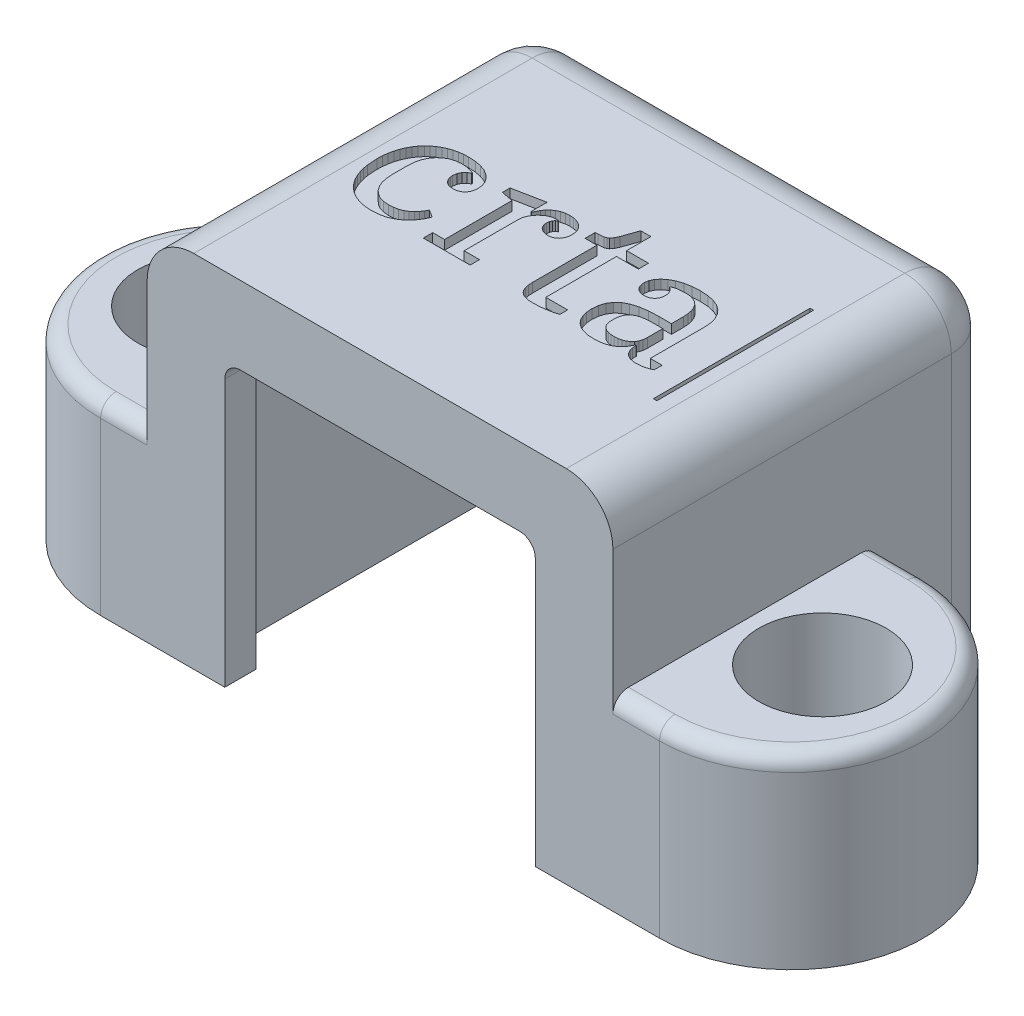
SolidWorks part; units mm, degrees
material "Custom Plastic"
ref_plane "Front Plane" through (0, 0, 0) normal (0, 0, 1) x (1, 0, 0)
ref_plane "Top Plane" through (0, 0, 0) normal (0, 1, 0) x (1, 0, 0)
ref_plane "Right Plane" through (0, 0, 0) normal (1, 0, 0) x (0, 0, -1)
sketch "Sketch1" plane through (0, 0, 0) normal (0, 0, 1) x (1, 0, 0)
  line L0 (0, -210.3757) -> (0, 10308.4069) construction
  line L1 (0, 0) -> (6, 0)
  line L2 (6, 0) -> (6, -10.1)
  line L3 (0, 1.5) -> (7.5, 1.5)
  line L4 (7.5, 1.5) -> (7.5, -10.1)
  line L5 (7.5, -10.1) -> (6, -10.1)
  line L6 (-7.5, -10.1) -> (-6, -10.1)
  line L7 (-7.5, 1.5) -> (-7.5, -10.1)
  line L8 (0, 1.5) -> (-7.5, 1.5)
  line L9 (-6, 0) -> (-6, -10.1)
  line L10 (0, 0) -> (-6, 0)
  dimension "D1" = 12
  dimension "D2" = 10.1
  dimension "D3" = 1.5
extrude "Boss-Extrude1" add sketch "Sketch1" along normal blind 12.4
sketch "Sketch3" plane through (0, -10.1, 0) normal (0, -1, 0) x (1, 0, 0)
  line L0 (0, -1000) -> (0, 49000) construction
  line L1 (7.5, 0) -> (-7.5, 0) construction
  line L2 (7.5, 3.9) -> (7.5, 12.4)
  line L3 (7.5, 12.4) -> (7.5, 0) construction
  line L4 (7.5, 3.9) -> (9, 3.9)
  line L5 (7.5, 12.4) -> (9, 12.4)
  line L6 (-7.5, 12.4) -> (-9, 12.4)
  line L7 (-7.5, 3.9) -> (-9, 3.9)
  line L8 (-7.5, 3.9) -> (-7.5, 12.4)
  arc A0 (9, 3.9) -> (9, 12.4) centre (9, 8.15) ccw
  arc A1 (-9, 3.9) -> (-9, 12.4) centre (-9, 8.15) cw
  point P5 (0, 0)
  point P10 (7.5, 8.15)
  point P22 (-7.5, 8.15)
  dimension "D1" = 8.5
  dimension "D2" = 1.5
extrude "Boss-Extrude2" add sketch "Sketch3" against normal blind 6
sketch "Sketch4" plane through (0, -10.1, 0) normal (0, -1, 0) x (1, 0, 0)
  line L1 (0, -1000) -> (0, 49000) construction
  circle A0 centre (-10, 8.15) radius 2.05
  circle A2 centre (10, 8.15) radius 2.05
  arc A3 (-9, 12.4) -> (-9, 3.9) centre (-9, 8.15) ccw construction
  point P3 (-9, 8.15)
  dimension "D1" = 4.1
  dimension "D2" = 1
extrude "Cut-Extrude1" cut sketch "Sketch4" against normal up to surface (6 mm away) up to face at (9.3125, -4.1, 8.15)
fillet "Fillet1" radius 1.5 2 edges at (-7.5, 1.5, 6.2) (7.5, 1.5, 6.2)
fillet "Fillet2" radius 0.5 6 edges at (8.25, -4.1, 3.9) (8.25, -4.1, 12.4) (13.25, -4.1, 8.15) (-8.25, -4.1, 12.4) (-13.25, -4.1, 8.15) (-8.25, -4.1, 3.9)
fillet "Fillet3" radius 1 2 edges at (-6, 0, 6.2) (6, 0, 6.2)
sketch "Sketch6" plane through (0, 0, 12.4) normal (0, 0, -1) x (-1, 0, 0)
  line L0 (6, -10.1) -> (6, -1) construction
  line L1 (5, 0) -> (-5, 0) construction
  line L2 (-6, -1) -> (-6, -10.1) construction
  line L3 (6, -10.1) -> (6, -1)
  line L4 (5, 0) -> (-5, 0)
  line L5 (-6, -1) -> (-6, -10.1)
  line L6 (5, -10.1) -> (5, -1)
  line L7 (5, -1) -> (-5, -1)
  line L8 (-5, -1) -> (-5, -10.1)
  line L9 (-5, -10.1) -> (-6, -10.1)
  line L10 (5, -10.1) -> (6, -10.1)
  arc A0 (6, -1) -> (5, 0) centre (5, -1) ccw construction
  arc A1 (-5, 0) -> (-6, -1) centre (-5, -1) ccw construction
  arc A2 (6, -1) -> (5, 0) centre (5, -1) ccw
  arc A3 (-5, 0) -> (-6, -1) centre (-5, -1) ccw
  arc A4 (5, -1) -> (5, -1) centre (5, -1) ccw
  arc A5 (-5, -1) -> (-5, -1) centre (-5, -1) ccw
  dimension "D1" = 1
extrude "Boss-Extrude3" add sketch "Sketch6" along normal blind 1
fillet "Fillet4" radius 0.5 2 edges at (-5, -1, 11.9) (5, -1, 11.9)
ref_plane "Plane1" through (0, 0, 5.55) normal (0, 0, -1) x (-1, 0, 0)
sketch "Sketch7" plane through (0, 0, 5.55) normal (0, 0, -1) x (-1, 0, 0)
  line L0 (-6, -2) -> (-4, 0)
  line L1 (-6, -1) -> (-6, -10.1) construction
  line L2 (5, 0) -> (-5, 0) construction
  line L3 (5, 0) -> (-5, 0) construction
  line L4 (-6, -1) -> (-6, -10.1) construction
  line L5 (-4, 0) -> (-5, 0)
  line L6 (-6, -1) -> (-6, -2)
  line L7 (0, -1000) -> (0, 49000) construction
  line L8 (6, -1) -> (6, -2)
  line L9 (4, 0) -> (5, 0)
  line L10 (6, -2) -> (4, 0)
  arc A0 (-5, 0) -> (-6, -1) centre (-5, -1) ccw construction
  arc A1 (-5, 0) -> (-6, -1) centre (-5, -1) ccw
  arc A2 (5, 0) -> (6, -1) centre (5, -1) cw
  dimension "D1" = 45
  dimension "D2" = 2
extrude "Boss-Extrude4" add sketch "Sketch7" along normal blind 1 contours L5 A1 L6 L0 | A2 L9 L10 L8 region at (5.28, -0.72, 5.55) region at (-5.28, -0.72, 5.55)
fillet "Fillet5" radius 1.5 5 edges at (-7.5, -5.05, 0) (-7.0607, 1.0607, 0) (0, 1.5, 0) (7.0607, 1.0607, 0) (7.5, -5.05, 0)
sketch "Sketch8" plane through (0, 1.5, 0) normal (0, 1, 0) x (1, 0, 0)
  point P306 (0, 0)
  line B0 (-4.3206, -8.3419) -> (-4.4819, -8.3349)
  line B1 (-4.4819, -8.3349) -> (-4.6341, -8.3138)
  line B2 (-4.6341, -8.3138) -> (-4.7771, -8.2786)
  line B3 (-4.7771, -8.2786) -> (-4.911, -8.2294)
  line B4 (-4.911, -8.2294) -> (-5.0326, -8.1676)
  line B5 (-5.0326, -8.1676) -> (-5.1444, -8.0945)
  line B6 (-5.1444, -8.0945) -> (-5.2463, -8.0101)
  line B7 (-5.2463, -8.0101) -> (-5.3384, -7.9146)
  line B8 (-5.3384, -7.9146) -> (-5.4203, -7.8084)
  line B9 (-5.4203, -7.8084) -> (-5.4916, -7.6924)
  line B10 (-5.4916, -7.6924) -> (-5.5524, -7.5666)
  line B11 (-5.5524, -7.5666) -> (-5.6027, -7.431)
  line B12 (-5.6027, -7.431) -> (-5.6421, -7.2869)
  line B13 (-5.6421, -7.2869) -> (-5.6702, -7.1357)
  line B14 (-5.6702, -7.1357) -> (-5.6927, -6.8124)
  line B15 (-5.6927, -6.8124) -> (-5.686, -6.6374)
  line B16 (-5.686, -6.6374) -> (-5.666, -6.4722)
  line B17 (-5.666, -6.4722) -> (-5.6326, -6.3169)
  line B18 (-5.6326, -6.3169) -> (-5.5858, -6.1714)
  line B19 (-5.5858, -6.1714) -> (-5.5271, -6.0336)
  line B20 (-5.5271, -6.0336) -> (-5.4579, -5.9071)
  line B21 (-5.4579, -5.9071) -> (-5.3781, -5.7918)
  line B22 (-5.3781, -5.7918) -> (-5.2878, -5.6878)
  line B23 (-5.2878, -5.6878) -> (-5.188, -5.5954)
  line B24 (-5.188, -5.5954) -> (-5.0797, -5.5149)
  line B25 (-5.0797, -5.5149) -> (-4.9631, -5.4463)
  line B26 (-4.9631, -5.4463) -> (-4.8379, -5.3898)
  line B27 (-4.8379, -5.3898) -> (-4.703, -5.343)
  line B28 (-4.703, -5.343) -> (-4.5624, -5.3096)
  line B29 (-4.5624, -5.3096) -> (-4.4162, -5.2896)
  line B30 (-4.4162, -5.2896) -> (-4.2644, -5.2829)
  line B31 (-4.2644, -5.2829) -> (-4.0359, -5.2956)
  line B32 (-4.0359, -5.2956) -> (-3.8342, -5.3335)
  line B33 (-3.8342, -5.3335) -> (-3.6592, -5.3968)
  line B34 (-3.6592, -5.3968) -> (-3.5109, -5.4853)
  line B35 (-3.5109, -5.4853) -> (-3.3903, -5.5936)
  line B36 (-3.3903, -5.5936) -> (-3.3042, -5.7159)
  line B37 (-3.3042, -5.7159) -> (-3.2526, -5.8523)
  line B38 (-3.2526, -5.8523) -> (-3.2353, -6.0027)
  line B39 (-3.2353, -6.0027) -> (-3.242, -6.0958)
  line B40 (-3.242, -6.0958) -> (-3.2621, -6.1784)
  line B41 (-3.2621, -6.1784) -> (-3.2954, -6.2505)
  line B42 (-3.2954, -6.2505) -> (-3.3422, -6.312)
  line B43 (-3.3422, -6.312) -> (-3.4002, -6.3587)
  line B44 (-3.4002, -6.3587) -> (-3.4673, -6.3921)
  line B45 (-3.4673, -6.3921) -> (-3.5436, -6.4121)
  line B46 (-3.5436, -6.4121) -> (-3.629, -6.4188)
  line B47 (-3.629, -6.4188) -> (-3.7161, -6.4125)
  line B48 (-3.7161, -6.4125) -> (-3.792, -6.3935)
  line B49 (-3.792, -6.3935) -> (-3.8567, -6.3619)
  line B50 (-3.8567, -6.3619) -> (-3.9101, -6.3176)
  line B51 (-3.9101, -6.3176) -> (-3.9519, -6.261)
  line B52 (-3.9519, -6.261) -> (-3.9818, -6.1981)
  line B53 (-3.9818, -6.1981) -> (-3.9997, -6.1289)
  line B54 (-3.9997, -6.1289) -> (-4.0057, -6.0533)
  line B55 (-4.0057, -6.0533) -> (-3.9889, -5.9324)
  line B56 (-3.9889, -5.9324) -> (-3.9382, -5.8284)
  line B57 (-3.9382, -5.8284) -> (-3.8609, -5.7454)
  line B58 (-3.8609, -5.7454) -> (-3.7639, -5.6878)
  line B59 (-3.7639, -5.6878) -> (-3.7639, -5.6597)
  line B60 (-3.7639, -5.6597) -> (-3.9326, -5.6091)
  line B61 (-3.9326, -5.6091) -> (-4.0465, -5.588)
  line B62 (-4.0465, -5.588) -> (-4.1857, -5.5809)
  line B63 (-4.1857, -5.5809) -> (-4.3628, -5.5978)
  line B64 (-4.3628, -5.5978) -> (-4.5231, -5.6484)
  line B65 (-4.5231, -5.6484) -> (-4.6636, -5.73)
  line B66 (-4.6636, -5.73) -> (-4.7817, -5.8396)
  line B67 (-4.7817, -5.8396) -> (-4.8773, -5.9703)
  line B68 (-4.8773, -5.9703) -> (-4.9504, -6.1264)
  line B69 (-4.9504, -6.1264) -> (-4.9926, -6.3049)
  line B70 (-4.9926, -6.3049) -> (-5.0066, -6.5031)
  line B71 (-5.0066, -6.5031) -> (-5.0066, -6.9924)
  line B72 (-5.0066, -6.9924) -> (-4.9936, -7.1923)
  line B73 (-4.9936, -7.1923) -> (-4.9546, -7.3705)
  line B74 (-4.9546, -7.3705) -> (-4.8896, -7.5269)
  line B75 (-4.8896, -7.5269) -> (-4.7986, -7.6615)
  line B76 (-4.7986, -7.6615) -> (-4.6851, -7.7673)
  line B77 (-4.6851, -7.7673) -> (-4.5526, -7.8429)
  line B78 (-4.5526, -7.8429) -> (-4.4011, -7.8882)
  line B79 (-4.4011, -7.8882) -> (-4.2306, -7.9033)
  line B80 (-4.2306, -7.9033) -> (-4.0714, -7.8942)
  line B81 (-4.0714, -7.8942) -> (-3.9312, -7.8668)
  line B82 (-3.9312, -7.8668) -> (-3.81, -7.8211)
  line B83 (-3.81, -7.8211) -> (-3.7077, -7.7571)
  line B84 (-3.7077, -7.7571) -> (-3.6177, -7.6798)
  line B85 (-3.6177, -7.6798) -> (-3.539, -7.594)
  line B86 (-3.539, -7.594) -> (-3.4715, -7.4998)
  line B87 (-3.4715, -7.4998) -> (-3.4153, -7.3972)
  line B88 (-3.4153, -7.3972) -> (-3.1735, -7.5434)
  line B89 (-3.1735, -7.5434) -> (-3.2354, -7.6882)
  line B90 (-3.2354, -7.6882) -> (-3.3197, -7.8302)
  line B91 (-3.3197, -7.8302) -> (-3.4265, -7.9652)
  line B92 (-3.4265, -7.9652) -> (-3.5559, -8.0889)
  line B93 (-3.5559, -8.0889) -> (-3.7091, -8.1915)
  line B94 (-3.7091, -8.1915) -> (-3.8876, -8.2744)
  line B95 (-3.8876, -8.2744) -> (-4.0915, -8.325)
  line B96 (-4.0915, -8.325) -> (-4.3206, -8.3419)
  line B97 (-2.7326, -7.9708) -> (-2.3502, -7.9708)
  line B98 (-2.3502, -7.9708) -> (-2.3502, -5.8002)
  line B99 (-2.3502, -5.8002) -> (-2.7326, -5.7271)
  line B100 (-2.7326, -5.7271) -> (-2.7326, -5.4797)
  line B101 (-2.7326, -5.4797) -> (-1.7373, -5.2829)
  line B102 (-1.7373, -5.2829) -> (-1.7373, -5.8059)
  line B103 (-1.7373, -5.8059) -> (-1.7091, -5.8059)
  line B104 (-1.7091, -5.8059) -> (-1.6136, -5.6147)
  line B105 (-1.6136, -5.6147) -> (-1.5461, -5.5247)
  line B106 (-1.5461, -5.5247) -> (-1.4674, -5.446)
  line B107 (-1.4674, -5.446) -> (-1.3718, -5.3799)
  line B108 (-1.3718, -5.3799) -> (-1.2649, -5.3279)
  line B109 (-1.2649, -5.3279) -> (-1.1398, -5.2942)
  line B110 (-1.1398, -5.2942) -> (-1.0006, -5.2829)
  line B111 (-1.0006, -5.2829) -> (-0.878, -5.291)
  line B112 (-0.878, -5.291) -> (-0.7687, -5.3153)
  line B113 (-0.7687, -5.3153) -> (-0.6727, -5.3557)
  line B114 (-0.6727, -5.3557) -> (-0.5901, -5.4122)
  line B115 (-0.5901, -5.4122) -> (-0.5213, -5.4839)
  line B116 (-0.5213, -5.4839) -> (-0.4721, -5.5697)
  line B117 (-0.4721, -5.5697) -> (-0.4425, -5.6695)
  line B118 (-0.4425, -5.6695) -> (-0.4327, -5.7834)
  line B119 (-0.4327, -5.7834) -> (-0.439, -5.8741)
  line B120 (-0.439, -5.8741) -> (-0.458, -5.9549)
  line B121 (-0.458, -5.9549) -> (-0.4896, -6.0259)
  line B122 (-0.4896, -6.0259) -> (-0.5339, -6.087)
  line B123 (-0.5339, -6.087) -> (-0.5863, -6.1338)
  line B124 (-0.5863, -6.1338) -> (-0.6478, -6.1672)
  line B125 (-0.6478, -6.1672) -> (-0.7184, -6.1872)
  line B126 (-0.7184, -6.1872) -> (-0.7982, -6.1939)
  line B127 (-0.7982, -6.1939) -> (-0.8808, -6.1882)
  line B128 (-0.8808, -6.1882) -> (-0.9542, -6.1714)
  line B129 (-0.9542, -6.1714) -> (-1.0186, -6.1433)
  line B130 (-1.0186, -6.1433) -> (-1.0737, -6.1039)
  line B131 (-1.0737, -6.1039) -> (-1.1155, -6.0533)
  line B132 (-1.1155, -6.0533) -> (-1.1454, -5.9971)
  line B133 (-1.1454, -5.9971) -> (-1.1633, -5.9352)
  line B134 (-1.1633, -5.9352) -> (-1.1693, -5.8677)
  line B135 (-1.1693, -5.8677) -> (-1.1595, -5.7806)
  line B136 (-1.1595, -5.7806) -> (-1.13, -5.7103)
  line B137 (-1.13, -5.7103) -> (-1.0864, -5.6569)
  line B138 (-1.0864, -5.6569) -> (-1.0344, -5.6316)
  line B139 (-1.0344, -5.6316) -> (-1.0344, -5.6147)
  line B140 (-1.0344, -5.6147) -> (-1.0737, -5.6091)
  line B141 (-1.0737, -5.6091) -> (-1.1412, -5.6034)
  line B142 (-1.1412, -5.6034) -> (-1.248, -5.6175)
  line B143 (-1.248, -5.6175) -> (-1.3549, -5.6597)
  line B144 (-1.3549, -5.6597) -> (-1.4519, -5.7243)
  line B145 (-1.4519, -5.7243) -> (-1.5405, -5.8059)
  line B146 (-1.5405, -5.8059) -> (-1.6121, -5.8972)
  line B147 (-1.6121, -5.8972) -> (-1.6698, -6.0027)
  line B148 (-1.6698, -6.0027) -> (-1.7077, -6.1095)
  line B149 (-1.7077, -6.1095) -> (-1.7204, -6.2164)
  line B150 (-1.7204, -6.2164) -> (-1.7204, -7.9708)
  line B151 (-1.7204, -7.9708) -> (-1.2256, -7.9708)
  line B152 (-1.2256, -7.9708) -> (-1.2256, -8.2744)
  line B153 (-1.2256, -8.2744) -> (-2.7326, -8.2744)
  line B154 (-2.7326, -8.2744) -> (-2.7326, -7.9708)
  line B155 (0.8414, -8.3194) -> (0.6931, -8.311)
  line B156 (0.6931, -8.311) -> (0.5687, -8.2857)
  line B157 (0.5687, -8.2857) -> (0.4682, -8.2435)
  line B158 (0.4682, -8.2435) -> (0.3916, -8.1845)
  line B159 (0.3916, -8.1845) -> (0.335, -8.1071)
  line B160 (0.335, -8.1071) -> (0.2946, -8.0101)
  line B161 (0.2946, -8.0101) -> (0.2703, -7.8935)
  line B162 (0.2703, -7.8935) -> (0.2623, -7.7571)
  line B163 (0.2623, -7.7571) -> (0.2623, -5.6765)
  line B164 (0.2623, -5.6765) -> (-0.1201, -5.6765)
  line B165 (-0.1201, -5.6765) -> (-0.1201, -5.3504)
  line B166 (-0.1201, -5.3504) -> (-0.0245, -5.3504)
  line B167 (-0.0245, -5.3504) -> (0.1512, -5.3321)
  line B168 (0.1512, -5.3321) -> (0.2148, -5.3093)
  line B169 (0.2148, -5.3093) -> (0.2623, -5.2773)
  line B170 (0.2623, -5.2773) -> (0.3339, -5.1873)
  line B171 (0.3339, -5.1873) -> (0.3916, -5.0636)
  line B172 (0.3916, -5.0636) -> (0.5659, -4.5688)
  line B173 (0.5659, -4.5688) -> (0.892, -4.5688)
  line B174 (0.892, -4.5688) -> (0.892, -5.3504)
  line B175 (0.892, -5.3504) -> (1.5949, -5.3504)
  line B176 (1.5949, -5.3504) -> (1.5949, -5.6765)
  line B177 (1.5949, -5.6765) -> (0.892, -5.6765)
  line B178 (0.892, -5.6765) -> (0.892, -7.9539)
  line B179 (0.892, -7.9539) -> (1.5949, -7.9539)
  line B180 (1.5949, -7.9539) -> (1.5949, -8.2013)
  line B181 (1.5949, -8.2013) -> (1.4698, -8.2435)
  line B182 (1.4698, -8.2435) -> (1.2857, -8.2801)
  line B183 (1.2857, -8.2801) -> (1.0706, -8.3096)
  line B184 (1.0706, -8.3096) -> (0.8414, -8.3194)
  line B185 (2.8339, -8.3419) -> (2.6279, -8.3286)
  line B186 (2.6279, -8.3286) -> (2.4487, -8.2885)
  line B187 (2.4487, -8.2885) -> (2.2962, -8.2217)
  line B188 (2.2962, -8.2217) -> (2.1703, -8.1282)
  line B189 (2.1703, -8.1282) -> (2.0744, -8.0087)
  line B190 (2.0744, -8.0087) -> (2.0059, -7.8696)
  line B191 (2.0059, -7.8696) -> (1.9647, -7.7107)
  line B192 (1.9647, -7.7107) -> (1.951, -7.5322)
  line B193 (1.951, -7.5322) -> (1.97, -7.3315)
  line B194 (1.97, -7.3315) -> (2.027, -7.1568)
  line B195 (2.027, -7.1568) -> (2.1218, -7.0082)
  line B196 (2.1218, -7.0082) -> (2.2547, -6.8855)
  line B197 (2.2547, -6.8855) -> (2.4304, -6.7896)
  line B198 (2.4304, -6.7896) -> (2.6539, -6.721)
  line B199 (2.6539, -6.721) -> (2.9253, -6.6799)
  line B200 (2.9253, -6.6799) -> (3.2444, -6.6662)
  line B201 (3.2444, -6.6662) -> (3.6492, -6.6662)
  line B202 (3.6492, -6.6662) -> (3.6492, -6.2838)
  line B203 (3.6492, -6.2838) -> (3.6397, -6.1225)
  line B204 (3.6397, -6.1225) -> (3.6113, -5.9816)
  line B205 (3.6113, -5.9816) -> (3.5638, -5.861)
  line B206 (3.5638, -5.861) -> (3.4974, -5.7609)
  line B207 (3.4974, -5.7609) -> (3.4106, -5.6822)
  line B208 (3.4106, -5.6822) -> (3.302, -5.6259)
  line B209 (3.302, -5.6259) -> (3.1716, -5.5922)
  line B210 (3.1716, -5.5922) -> (3.0194, -5.5809)
  line B211 (3.0194, -5.5809) -> (2.7776, -5.6006)
  line B212 (2.7776, -5.6006) -> (2.6821, -5.6252)
  line B213 (2.6821, -5.6252) -> (2.6033, -5.6597)
  line B214 (2.6033, -5.6597) -> (2.6033, -5.6822)
  line B215 (2.6033, -5.6822) -> (2.6624, -5.7215)
  line B216 (2.6624, -5.7215) -> (2.7158, -5.7834)
  line B217 (2.7158, -5.7834) -> (2.758, -5.8649)
  line B218 (2.758, -5.8649) -> (2.772, -5.9746)
  line B219 (2.772, -5.9746) -> (2.766, -6.0494)
  line B220 (2.766, -6.0494) -> (2.7481, -6.1166)
  line B221 (2.7481, -6.1166) -> (2.7182, -6.1759)
  line B222 (2.7182, -6.1759) -> (2.6764, -6.2276)
  line B223 (2.6764, -6.2276) -> (2.6262, -6.2694)
  line B224 (2.6262, -6.2694) -> (2.5654, -6.2993)
  line B225 (2.5654, -6.2993) -> (2.494, -6.3172)
  line B226 (2.494, -6.3172) -> (2.4121, -6.3232)
  line B227 (2.4121, -6.3232) -> (2.3419, -6.3172)
  line B228 (2.3419, -6.3172) -> (2.2772, -6.2993)
  line B229 (2.2772, -6.2993) -> (2.2181, -6.2694)
  line B230 (2.2181, -6.2694) -> (2.1647, -6.2276)
  line B231 (2.1647, -6.2276) -> (2.1229, -6.1728)
  line B232 (2.1229, -6.1728) -> (2.093, -6.1095)
  line B233 (2.093, -6.1095) -> (2.0751, -6.0378)
  line B234 (2.0751, -6.0378) -> (2.0691, -5.9577)
  line B235 (2.0691, -5.9577) -> (2.0874, -5.8312)
  line B236 (2.0874, -5.8312) -> (2.1422, -5.7103)
  line B237 (2.1422, -5.7103) -> (2.2378, -5.5936)
  line B238 (2.2378, -5.5936) -> (2.3672, -5.491)
  line B239 (2.3672, -5.491) -> (2.5288, -5.4052)
  line B240 (2.5288, -5.4052) -> (2.7214, -5.3391)
  line B241 (2.7214, -5.3391) -> (2.9506, -5.297)
  line B242 (2.9506, -5.297) -> (3.2106, -5.2829)
  line B243 (3.2106, -5.2829) -> (3.4588, -5.2984)
  line B244 (3.4588, -5.2984) -> (3.6745, -5.3448)
  line B245 (3.6745, -5.3448) -> (3.858, -5.4221)
  line B246 (3.858, -5.4221) -> (4.0091, -5.5303)
  line B247 (4.0091, -5.5303) -> (4.1272, -5.6663)
  line B248 (4.1272, -5.6663) -> (4.2116, -5.8269)
  line B249 (4.2116, -5.8269) -> (4.2622, -6.0122)
  line B250 (4.2622, -6.0122) -> (4.279, -6.222)
  line B251 (4.279, -6.222) -> (4.279, -7.9764)
  line B252 (4.279, -7.9764) -> (4.6614, -7.9764)
  line B253 (4.6614, -7.9764) -> (4.6614, -8.2294)
  line B254 (4.6614, -8.2294) -> (4.5714, -8.2716)
  line B255 (4.5714, -8.2716) -> (4.459, -8.3082)
  line B256 (4.459, -8.3082) -> (4.331, -8.3335)
  line B257 (4.331, -8.3335) -> (4.1947, -8.3419)
  line B258 (4.1947, -8.3419) -> (4.0738, -8.3338)
  line B259 (4.0738, -8.3338) -> (3.9698, -8.3096)
  line B260 (3.9698, -8.3096) -> (3.8826, -8.2692)
  line B261 (3.8826, -8.2692) -> (3.8123, -8.2126)
  line B262 (3.8123, -8.2126) -> (3.7606, -8.1405)
  line B263 (3.7606, -8.1405) -> (3.7237, -8.0593)
  line B264 (3.7237, -8.0593) -> (3.7016, -7.969)
  line B265 (3.7016, -7.969) -> (3.6942, -7.8696)
  line B266 (3.6942, -7.8696) -> (3.6942, -7.8414)
  line B267 (3.6942, -7.8414) -> (3.6661, -7.8414)
  line B268 (3.6661, -7.8414) -> (3.5649, -8.027)
  line B269 (3.5649, -8.027) -> (3.4932, -8.1085)
  line B270 (3.4932, -8.1085) -> (3.4018, -8.1845)
  line B271 (3.4018, -8.1845) -> (3.295, -8.2491)
  line B272 (3.295, -8.2491) -> (3.1656, -8.2969)
  line B273 (3.1656, -8.2969) -> (3.0124, -8.3307)
  line B274 (3.0124, -8.3307) -> (2.8339, -8.3419)
  line B275 (3.0813, -7.9483) -> (3.1994, -7.9409)
  line B276 (3.1994, -7.9409) -> (3.3062, -7.9188)
  line B277 (3.3062, -7.9188) -> (3.4018, -7.8819)
  line B278 (3.4018, -7.8819) -> (3.4862, -7.8302)
  line B279 (3.4862, -7.8302) -> (3.5575, -7.7617)
  line B280 (3.5575, -7.7617) -> (3.6085, -7.6742)
  line B281 (3.6085, -7.6742) -> (3.639, -7.5677)
  line B282 (3.639, -7.5677) -> (3.6492, -7.4422)
  line B283 (3.6492, -7.4422) -> (3.6492, -6.9417)
  line B284 (3.6492, -6.9417) -> (3.3118, -6.9417)
  line B285 (3.3118, -6.9417) -> (3.1273, -6.9498)
  line B286 (3.1273, -6.9498) -> (2.9731, -6.9741)
  line B287 (2.9731, -6.9741) -> (2.849, -7.0145)
  line B288 (2.849, -7.0145) -> (2.7552, -7.0711)
  line B289 (2.7552, -7.0711) -> (2.6863, -7.1428)
  line B290 (2.6863, -7.1428) -> (2.6371, -7.2285)
  line B291 (2.6371, -7.2285) -> (2.6075, -7.3283)
  line B292 (2.6075, -7.3283) -> (2.5977, -7.4422)
  line B293 (2.5977, -7.4422) -> (2.5977, -7.549)
  line B294 (2.5977, -7.549) -> (2.6058, -7.6439)
  line B295 (2.6058, -7.6439) -> (2.63, -7.7262)
  line B296 (2.63, -7.7262) -> (2.6705, -7.7958)
  line B297 (2.6705, -7.7958) -> (2.727, -7.8527)
  line B298 (2.727, -7.8527) -> (2.7977, -7.8945)
  line B299 (2.7977, -7.8945) -> (2.8803, -7.9244)
  line B300 (2.8803, -7.9244) -> (2.9748, -7.9423)
  line B301 (2.9748, -7.9423) -> (3.0813, -7.9483)
  line B302 (5.4528, -4.0008) -> (5.5652, -4.0008)
  line B303 (5.5652, -4.0008) -> (5.5652, -9.0504)
  line B304 (5.5652, -9.0504) -> (5.4528, -9.0504)
  line B305 (5.4528, -9.0504) -> (5.4528, -4.0008)
sketch_block_instance "Block1-1"
sketch_block "Block1"
extrude "Cut-Extrude2" cut sketch "Sketch8" against normal blind 0.3
equation "\"Hole_Diameter\"= 4.1mm"
equation "\"Hole_Depth\"= 6mm"
equation "\"D1@Sketch4\"=\"Hole_Diameter\""
equation "\"D1@Boss-Extrude2\"=\"Hole_Depth\""
